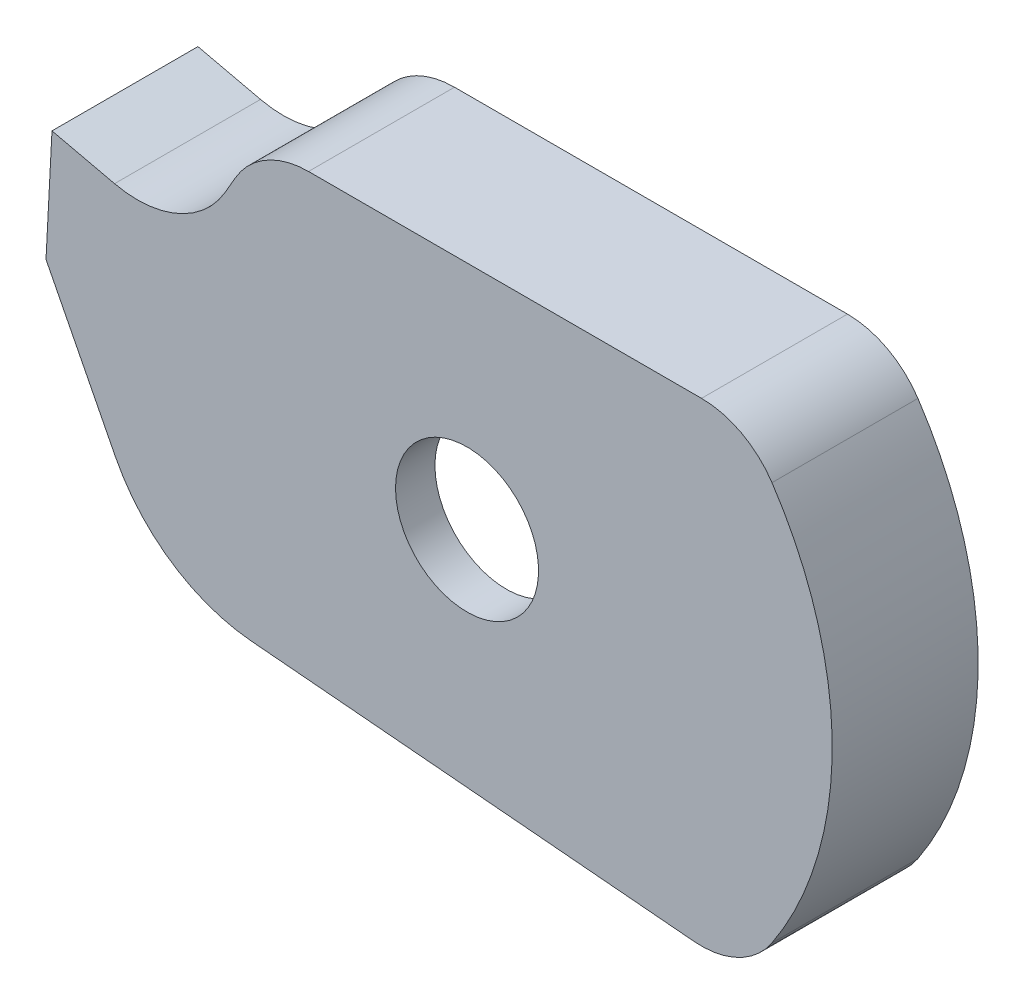
SolidWorks part; units mm, degrees
material "AISI 4340 Aço, normalizado"
ref_plane "Plano frontal" through (0, 0, 0) normal (0, 0, 1) x (1, 0, 0)
ref_plane "Plano superior" through (0, 0, 0) normal (0, 1, 0) x (1, 0, 0)
ref_plane "Plano direito" through (0, 0, 0) normal (1, 0, 0) x (0, 0, -1)
other "Center of Mass"
sketch "Sketch2" plane through (0, 0, 0) normal (0, 0, 1) x (1, 0, 0)
  line L0 (0, 0) -> (-50, 0) construction
  line L1 (-122.611, 44.3511) -> (-144.0471, 49.3)
  line L2 (0, 0) -> (-150.7683, 21.1891) construction
  line L5 (-56.158, 81.2) -> (78.4743, 81.2)
  line L6 (0, 0) -> (0, 41.2714) construction
  line L8 (-81.2728, 66.7) -> (-84.645, 60.8592)
  line L14 (-75.7112, -67.9381) -> (75.8733, -81.2)
  line L19 (-144.0471, 49.3) -> (-146.0989, 10.15)
  line L20 (-144.5576, 47.0888) -> (-142.8521, 54.4762) construction
  line L22 (-146.0989, 10.15) -> (-122.3345, -36.4902)
  circle A0 centre (0, 0) radius 152.25 construction
  arc A5 (78.4743, 81.2) -> (102.6203, 68.2615) centre (78.4743, 52.2) cw
  arc A6 (-56.158, 81.2) -> (-81.2728, 66.7) centre (-56.158, 52.2) ccw
  arc A17 (-122.3345, -36.4902) -> (-75.7112, -67.9381) centre (-70.6561, -10.1588) ccw
  arc A18 (-122.611, 44.3511) -> (-84.645, 60.8592) centre (-114.7827, 78.2592) ccw
  arc A20 (102.6203, 68.2615) -> (102.5242, -68.4058) centre (0, 0) cw
  arc A21 (75.8733, -81.2) -> (102.5242, -68.4058) centre (78.4008, -52.3104) ccw
  point P29 (-152.25, 0)
  point P31 (29.3939, 81.2)
  point P32 (-72.9012, 81.2)
  point P33 (102.6203, -68.2615)
  dimension "D1" = 304.5
  dimension "D4" = 29
  dimension "D5" = 34.8
  dimension "D13" = 29
  dimension "D11" = 58
  dimension "D10" = 81.2
  dimension "D2" = 5
  dimension "D3" = 10
  dimension "D7" = 30
  dimension "D8" = 77
  dimension "D12" = 30
  dimension "D9" = 49.3
  dimension "D14" = 39.15
  dimension "D15" = 22
  dimension "D6" = 29
  dimension "D16" = 5
  dimension "D17" = 81.2
extrude "EXTRUSÃO ESQ" add sketch "Sketch2" along normal blind 50 contours L5 A5 A20 A21 L14 A17 L22 L19 L1 A18 L8 A6
other "Ponto de referência do centro da massa1"
ref_plane "Plano2" through (0, 2.135, 0) normal (0, -1, 0) x (-1, 0, 0)
ref_plane "Plano3" through (-1.8584, 0, 0) normal (1, 0, 0) x (0, 0, -1)
sketch "Esboço2" plane through (0, 0, 0) normal (0, 0, -1) x (-1, 0, 0)
  line L0 (-8.25, 2.135) -> (8.25, 2.135) construction
  line L1 (-47.2035, 58.0719) -> (40.4617, 65.7416)
  line L2 (-61.7481, 40.7383) -> (-54.0784, -46.9269)
  line L3 (-36.7448, -61.4715) -> (50.9203, -53.8018)
  line L4 (57.7953, 51.1969) -> (65.465, -36.4682)
  line L5 (-63.1426, 56.6774) -> (66.8595, -52.4073) construction
  line L6 (-52.6839, -62.866) -> (56.4008, 67.1361) construction
  line L7 (1.8584, 8.25) -> (1.8584, -8.25) construction
  line L8 (75.7112, -67.9381) -> (-75.8733, -81.2) construction
  line L10 (2.503, 2.135) -> (86.0271, 2.135) construction
  circle A0 centre (1.8584, 2.135) radius 24.5
  arc A2 (-47.2035, 58.0719) -> (-61.7481, 40.7383) centre (-45.809, 42.1327) ccw
  arc A3 (40.4617, 65.7416) -> (57.7953, 51.1969) centre (41.8561, 49.8024) cw
  arc A4 (50.9203, -53.8018) -> (65.465, -36.4682) centre (49.5258, -37.8627) ccw
  arc A5 (-54.0784, -46.9269) -> (-36.7448, -61.4715) centre (-38.1393, -45.5324) ccw
  circle A6 centre (1.8584, 2.135) radius 42.5
  dimension "D1" = 16
  dimension "D2" = 49
  dimension "D5" = 85
  dimension "D3" = 120
  dimension "D4" = 120
extrude "REBAIXO CAMISA" cut sketch "Esboço2" against normal blind 36.5 contours L1 A3 L4 A4 L3 A5 L2 A2
extrude "FURO EIXO" cut sketch "Esboço2<3>" against normal through all contours A0
sketch "Esboço2<3>" plane through (0, 0, 0) normal (0, 0, -1) x (-1, 0, 0) same geometry as "Esboço2"
chamfer "CHANFRO CAMISA" [suppressed] distance 1 angle 45
sketch "REF. POLIA" plane through (0, 0, 0) normal (0, 0, -1) x (-1, 0, 0)
  circle A0 centre (1.8584, 2.135) radius 71
  circle A1 centre (1.8584, 2.135) radius 24.5 construction
  dimension "D1" = 142
fillet "Filete1" radius 7 8 edges at (58.0657, 52.4173, 0) (57.9133, -3.0943, 0) (48.4239, -57.7891, 0) (-7.0878, -57.6367, 0) (-61.7826, -48.1473, 0) (-61.6301, 7.3644, 0) (-52.1407, 62.0592, 0) (3.3709, 61.9067, 0)
equation "\"escala\" = 1                                            'projeto - escala geral"
equation "\"escala_disco-arma\"= 2.9                               'disco arma - escala geometria disco arma"
equation "\"rolamento_D-ext\"= 85                                   'rolamento arma - diametro externo"
equation "\"rolamento_d-int\"= 45                                   'rolamento arma - diametro interno"
equation "\"rolamento_b-esp\"= 23                                   'rolamento arma - espessura"
equation "\"arma_rebaixo-camisa_b\"= \"rolamento_b-esp\" + (\"arma-espessura\"-\"rolamento_b-esp\")/2        'disco arma - profundidade rebaixo camisa"
equation "\"arma-espessura\"= 50                                    'disco arma - espessura disco arma"
equation "\"D1@EXTRUSÃO ESQ\"=\"arma-espessura\""
equation "\"eixo_diam\"= \"rolamento_d-int\"                          'eixo arma - diametro"
equation "\"D2@Esboço2\" = \"eixo_diam\" + \"arma_eixo-furo_folga\""
equation "\"camisa_largura\"=120                                    'camisa arma - tamanho do lado"
equation "\"D3@Esboço2\"=\"camisa_largura\""
equation "\"camisa_raio\"=5                                        'camisa arma - raio canto interno"
equation "\"arma_rebaixo-camisa_raio\" = 16      'raio do rebaixo da camisa da arma "
equation "\"D1@Esboço2\"=\"arma_rebaixo-camisa_raio\""
equation "\"arma_alivio_raio\"= 12 * \"escala_disco-arma\""
equation "\"arma_diam_max\"= 105 * \"escala_disco-arma\""
equation "\"D1@Sketch2\" = \"arma_diam_max\""
equation "\"arma_arestas_raio\"= 10 * \"escala_disco-arma\""
equation "\"D4@Sketch2\" = \"arma_arestas_raio\""
equation "\"arma_altura_superior-centro\"= 28 * \"escala_disco-arma\""
equation "\"D10@Sketch2\" = \"arma_altura_superior-centro\""
equation "\"arma_dente_raio\"= 12 * \"escala_disco-arma\""
equation "\"D5@Sketch2\" = \"arma_dente_raio\""
equation "\"arma_altura_dente-centro\"= 17 * \"escala_disco-arma\""
equation "\"D9@Sketch2\"=\"arma_altura_dente-centro\""
equation "\"arma_dente_altura\"= 13.5 * \"escala_disco-arma\""
equation "\"arma_alivio-dente_raio\"= 20 * \"escala_disco-arma\""
equation "\"arma_traseira_offset\"= 10 * \"escala_disco-arma\""
equation "\"arma_centralizacao_offset\"= 8 * \"escala_disco-arma\""
equation "\"arma_eixo-furo_folga\" = 4                              'arma - folga entre furo arma e eixo"
equation "\"D1@REBAIXO CAMISA\" = \"arma_rebaixo-camisa_b\""
equation "\"D6@Sketch2\"=\"arma_traseira_offset\""
equation "\"D11@Sketch2\"=\"arma_alivio-dente_raio\""
equation "\"D4@Esboço2\"=\"camisa_largura\""
equation "\"D14@Sketch2\"=\"arma_dente_altura\""
equation "\"arma_altura_inferior-centro\"= 28 * \"escala_disco-arma\""
equation "\"D17@Sketch2\"=\"arma_altura_inferior-centro\""
equation "\"D13@Sketch2\"=\"arma_arestas_raio\""
equation "\"D5@Esboço2\"=\"rolamento_D-ext\""
equation "\"polia_diam_eff\" = 142"
equation "\"D1@REF. POLIA\" = \"polia_diam_eff\""
equation "\"arma_dente_comprimento\"=22"
equation "\"D15@Sketch2\"=\"arma_dente_comprimento\""
equation "\"camisa_rebaixo_rolamento\" = 1 * \"rolamento_b-esp\""
equation "\"polia_espessura\" = 40  "
